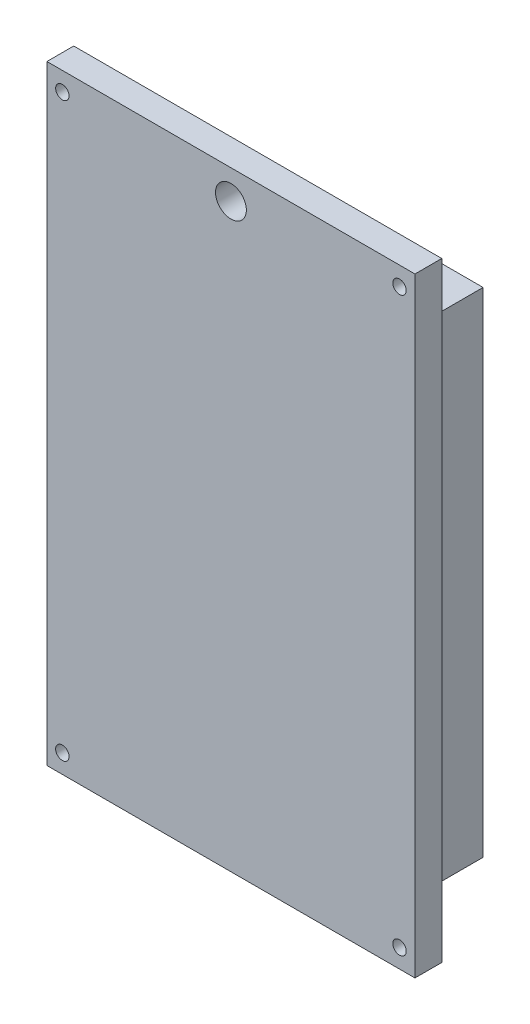
SolidWorks part; units mm, degrees
ref_plane "Front" through (0, 0, 0) normal (0, 0, 1) x (1, 0, 0)
ref_plane "Top" through (0, 0, 0) normal (0, 1, 0) x (1, 0, 0)
ref_plane "Right" through (0, 0, 0) normal (1, 0, 0) x (0, 0, -1)
sketch "arduinoOutline" plane through (0, 0, 0) normal (0, 0, 1) x (1, 0, 0)
  line L0 (0, 32.73) -> (2.54, 35.27) construction
  line L2 (0, 0) -> (0, 32.73) construction
  line L5 (2.54, 35.27) -> (2.54, 36.81) construction
  line L6 (3.54, 37.81) -> (67.6, 37.81) construction
  line L7 (68.6, 36.81) -> (68.6, -14.59) construction
  line L8 (67.6, -15.59) -> (4.06, -15.59) construction
  line L9 (4.06, -15.59) -> (2.54, -14.07) construction
  line L10 (2.54, -14.07) -> (2.54, -2.54) construction
  line L11 (2.54, -2.54) -> (0, 0) construction
  arc A0 (2.54, 36.81) -> (3.54, 37.81) centre (3.54, 36.81) cw construction
  arc A1 (68.6, -14.59) -> (67.6, -15.59) centre (67.6, -14.59) cw construction
  arc A2 (67.6, 37.81) -> (68.6, 36.81) centre (67.6, 36.81) cw construction
  point P8 (2.54, 37.81)
  point P13 (68.6, -15.59)
  point P16 (68.6, 37.81)
  dimension "D6" = 1
  dimension "D9" = 1
  dimension "D10" = 1
  dimension "D1" = 32.73
  dimension "D2" = 135
  dimension "D3" = 3.5921
  dimension "D4" = 2.54
  dimension "D5" = 66.06
  dimension "D7" = 53.4
  dimension "D8" = 64.54
  dimension "D11" = 135
  dimension "D12" = 2.1496
  dimension "D13" = 11.53
  dimension "D14" = 135
  dimension "D15" = 3.5921
sketch "arduinoMountingHolesSketch" plane through (0, 0, 0) normal (0, 0, 1) x (1, 0, 0)
  line L0 (0, 0) -> (0, 32.73) construction
  line L1 (67.6, -15.59) -> (4.06, -15.59) construction
  line L2 (3.54, 37.81) -> (67.6, 37.81) construction
  line L3 (68.6, 36.81) -> (68.6, -14.59) construction
  circle A0 centre (2.54, 2.28) radius 1.25
  circle A1 centre (2.54, 30.45) radius 1.25
  circle A2 centre (54.6, 35.27) radius 1.25
  circle A3 centre (53.35, -13.05) radius 1.25
  dimension "D9" = 2.5
  dimension "D1" = 2.54
  dimension "D2" = 17.87
  dimension "D3" = 2.54
  dimension "D4" = 7.36
  dimension "D5" = 2.54
  dimension "D6" = 14
  dimension "D7" = 2.54
  dimension "D8" = 15.25
sketch "9VbatteryMountingHolesSketch" plane through (0, 0, 0) normal (0, 0, 1) x (1, 0, 0)
  line L0 (0, 16.365) -> (68.6, 16.365) construction
  line L1 (4.875, 40.31) -> (63.725, 40.31) construction
  line L2 (4.875, 40.31) -> (4.875, 88.56) construction
  line L3 (4.875, 88.56) -> (63.725, 88.56) construction
  line L4 (63.725, 40.31) -> (63.725, 88.56) construction
  line L5 (0, 0) -> (0, 32.73) construction
  line L6 (68.6, 36.81) -> (68.6, -14.59) construction
  line L7 (34.3, 40.31) -> (34.3, 88.56) construction
  line L8 (4.875, 64.435) -> (63.725, 64.435) construction
  line L10 (3.54, 37.81) -> (67.6, 37.81) construction
  circle A0 centre (8.625, 86.06) radius 1.25
  circle A1 centre (59.975, 86.06) radius 1.25
  circle A2 centre (8.625, 42.81) radius 1.25
  circle A3 centre (59.975, 42.81) radius 1.25
  point P4 (34.3, 16.365)
  point P5 (34.3, 88.56)
  dimension "D3" = 2.5
  dimension "D1" = 48.25
  dimension "D2" = 58.85
  dimension "D4" = 2.5
  dimension "D5" = 3.75
  dimension "D6" = 2.5
sketch "legBracketMountingHolesSketch" plane through (0, 0, 0) normal (0, 0, 1) x (1, 0, 0)
  line L0 (34.3, 91.06) -> (34.3, 98.06) construction
  line L1 (24.1051, 98.06) -> (44.4949, 98.06) construction
  line L2 (24.1051, 98.06) -> (24.1051, 91.06) construction
  line L3 (24.1051, 91.06) -> (44.4949, 91.06) construction
  line L4 (44.4949, 98.06) -> (44.4949, 91.06) construction
  circle A0 centre (29.2026, 94.56) radius 2
  circle A1 centre (39.3974, 94.56) radius 2
  point P4 (24.1051, 94.56)
  point P5 (34.3, 98.06)
  dimension "D4" = 4
  dimension "D1" = 7
  dimension "D2" = 20.3898
  dimension "D3" = 2.5
  dimension "D5" = 5.0974
sketch "backsideMountingHolesSketch" plane through (0, 0, 0) normal (0, 0, 1) x (1, 0, 0)
  line L0 (0, 41.235) -> (68.6, 41.235) construction
  line L9 (0, 0) -> (0, 32.73) construction
  line L10 (34.3, 40.31) -> (34.3, 88.56) construction
  line L11 (68.6, 36.81) -> (68.6, -14.59) construction
  line L12 (24.1051, 98.06) -> (44.4949, 98.06) construction
  line L13 (4.875, 88.56) -> (63.725, 88.56) construction
  line L14 (4.875, 40.31) -> (4.875, 88.56) construction
  circle A1 centre (2.875, 94.56) radius 1.25
  circle A5 centre (65.725, 94.56) radius 1.25
  circle A6 centre (65.725, -12.09) radius 1.25
  circle A7 centre (2.875, -12.09) radius 1.25
  dimension "D1" = 2.5
  dimension "D2" = 56.825
  dimension "D3" = 6
  dimension "D4" = 2
sketch "Sketch1" plane through (0, 0, 0) normal (0, 0, 1) x (1, 0, 0)
  line L0 (67.6, -15.59) -> (4.06, -15.59) construction
  line L1 (0, 98.06) -> (68.6, 98.06)
  line L2 (0, 98.06) -> (0, -15.59)
  line L3 (0, -15.59) -> (68.6, -15.59)
  line L4 (68.6, 98.06) -> (68.6, -15.59)
  line L5 (0, 0) -> (0, 32.73) construction
  line L6 (68.6, 36.81) -> (68.6, -14.59) construction
  line L9 (24.1051, 98.06) -> (44.4949, 98.06) construction
extrude "bracketBase" add sketch "Sketch1" along normal blind 5
extrude "arduinoMountingHoles" cut sketch "arduinoMountingHolesSketch" against normal through all and the other way blind 22
extrude "9VbatteryMountingHoles" cut sketch "9VbatteryMountingHolesSketch" along normal blind 20
extrude "legBracketMountingHoles" cut sketch "legBracketMountingHolesSketch" along normal blind 13
extrude "backsideMountingHoles" cut sketch "backsideMountingHolesSketch" along normal blind 24
sketch "Sketch2" plane through (0, 0, 5) normal (0, 0, 1) x (1, 0, 0)
  circle A0 centre (53.35, -13.05) radius 1.25 construction
  circle A1 centre (2.54, 2.28) radius 1.25 construction
  circle A2 centre (2.54, 30.45) radius 1.25 construction
  circle A3 centre (54.6, 35.27) radius 1.25 construction
  circle A4 centre (59.975, 42.81) radius 1.25 construction
  circle A5 centre (8.625, 42.81) radius 1.25 construction
  circle A6 centre (59.975, 86.06) radius 1.25 construction
  circle A7 centre (39.3974, 94.56) radius 2 construction
  circle A8 centre (29.2026, 94.56) radius 2 construction
  circle A9 centre (8.625, 86.06) radius 1.25 construction
  circle A10 centre (53.35, -13.05) radius 1.25
  circle A11 centre (2.54, 2.28) radius 1.25
  circle A12 centre (2.54, 30.45) radius 1.25
  circle A13 centre (54.6, 35.27) radius 1.25
  circle A14 centre (59.975, 42.81) radius 1.25
  circle A15 centre (8.625, 42.81) radius 1.25
  circle A16 centre (59.975, 86.06) radius 1.25
  circle A17 centre (39.3974, 94.56) radius 2
  circle A18 centre (29.2026, 94.56) radius 2
  circle A19 centre (8.625, 86.06) radius 1.25
extrude "cover" add sketch "Sketch2" against normal up to surface (5 mm away) up to face at (1.625, -12.09, 0)
sketch "Sketch3" plane through (0, 0, 5) normal (0, 0, 1) x (1, 0, 0)
  line L1 (68.6, 98.06) -> (0, 98.06) construction
  line L2 (0, 98.06) -> (0, -15.59) construction
  line L3 (2.3, -4.765) -> (2.3, 87.235)
  line L4 (5.3, -1.765) -> (63.3, -1.765)
  line L5 (5.3, -1.765) -> (5.3, 84.235)
  line L6 (5.3, 84.235) -> (63.3, 84.235)
  line L7 (63.3, -1.765) -> (63.3, 84.235)
  line L8 (5.3, -1.765) -> (63.3, 84.235) construction
  line L9 (5.3, 84.235) -> (63.3, -1.765) construction
  line L10 (2.3, 87.235) -> (66.3, 87.235)
  line L11 (66.3, -4.765) -> (66.3, 87.235)
  line L12 (2.3, -4.765) -> (66.3, -4.765)
  point P4 (34.3, 98.06)
  point P5 (0, 41.235)
  point P6 (34.3, 41.235)
  dimension "D1" = 86
  dimension "D2" = 58
  dimension "D3" = 3
extrude "breadBoardCavity" add sketch "Sketch3" along normal blind 10
ref_plane "Plane1" through (0, 0, 2.5) normal (0, 0, 1) x (1, 0, 0)
mirror "Mirror1" about plane through (0, 0, 2.5) normal (0, 0, 1) of "breadBoardCavity"
sketch "Sketch4" plane through (0, 87.235, 0) normal (0, 1, 0) x (1, 0, 0)
  line L4 (66.3, -5) -> (2.3, -5)
  line L5 (2.3, -5) -> (2.3, -15)
  line L6 (2.3, -15) -> (66.3, -15)
  line L7 (66.3, -15) -> (66.3, -5)
  line L8 (66.3, -5) -> (2.3, -5)
  line L9 (2.3, -5) -> (2.3, -15)
  line L10 (2.3, -15) -> (66.3, -15)
  line L11 (66.3, -15) -> (66.3, -5)
  dimension "D1" = 0
extrude "Cut-Extrude1" cut sketch "Sketch4" against normal through all
sketch "Sketch5" plane through (0, 0, 0) normal (0, 0, -1) x (-1, 0, 0)
  line L1 (-68.6, 98.06) -> (0, 98.06) construction
  circle A0 centre (-34.3, 92.6475) radius 2.875
  point P2 (-34.3, 98.06)
  point P9 (-34.3, 95.5225)
  dimension "D1" = 5.75
  dimension "D2" = 5.4125
extrude "toggleSwitchHole" cut sketch "Sketch5" against normal blind 10
equation "\"D2@backsideMountingHolesSketch\"=113.65mm/2"
equation "\"D2@Sketch5\"=10.825mm/2"
